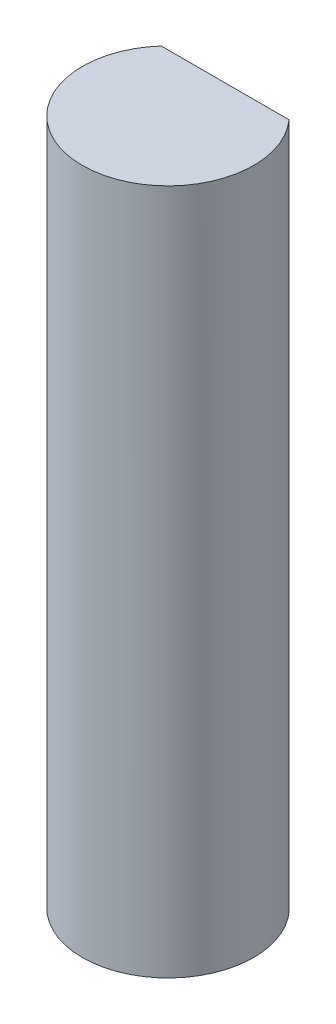
SolidWorks part; units mm, degrees
material "不锈钢 (铁素体)"
ref_plane "前视基准面" through (0, 0, 0) normal (0, 0, 1) x (1, 0, 0)
ref_plane "上视基准面" through (0, 0, 0) normal (0, 1, 0) x (1, 0, 0)
ref_plane "右视基准面" through (0, 0, 0) normal (1, 0, 0) x (0, 0, -1)
sketch "草图1" plane through (0, 0, 0) normal (0, 1, 0) x (1, 0, 0)
  circle A0 centre (0, 0) radius 1.5
extrude "凸台-拉伸1" add sketch "草图1" along normal blind 10
sketch "草图2" plane through (0, 10, 0) normal (0, 1, 0) x (1, 0, 0)
  line L0 (-1.118, 1) -> (1.118, 1)
  circle A0 centre (0, 0) radius 1.5 construction
  arc A1 (1.118, 1) -> (-1.118, 1) centre (0, 0) ccw
  dimension "D1" = 1
extrude "切除-拉伸1" cut sketch "草图2" against normal blind 10
sketch "草图3" [suppressed] plane through (0, 0, 0) normal (0, 0, 1) x (1, 0, 0)
  line L0 (-2.0153, 32) -> (-1.5, 32)
  line L1 (-1.5, 36) -> (-1.5, 0) construction
  line L2 (-1.5, 32) -> (-1.2504, 31.7363)
  line L3 (-1.2504, 31.7363) -> (-1.5, 31.5)
  line L4 (-1.5, 31.5) -> (-2.0153, 31.5)
  line L5 (-2.0153, 31.5) -> (-2.0153, 32)
  line L6 (1.5, 36) -> (-1.5, 36) construction
  line L7 (0, 0) -> (0, 36) construction
  dimension "D1" = 0.5
  dimension "D2" = 4
  dimension "D3" = 0.2496
revolve "切除-旋转1" [suppressed] cut sketch "草图3" angle 360 about L7
ref_axis "基准轴1" [suppressed] through (0, 37.8, 0) along (0, -1, 0)
pattern_linear "阵列(线性)1" [suppressed] count 60 spacing 0.5 along (0, -1, 0) of bodies 109
chamfer "倒角1" [suppressed] distance 0.1 angle 45
sketch "Sketch1" plane through (0, 0, 0) normal (0, -1, 0) x (1, 0, 0)
  circle A0 centre (0, 0) radius 1.5
extrude "Boss-Extrude1" add sketch "Sketch1" along normal blind 2
